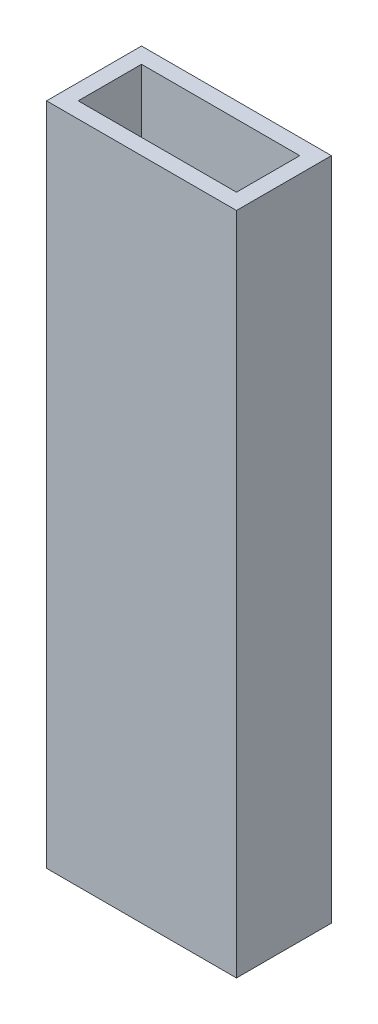
SolidWorks part; units mm, degrees
ref_plane "Front Plane" through (0, 0, 0) normal (0, 0, 1) x (1, 0, 0)
ref_plane "Top Plane" through (0, 0, 0) normal (0, 1, 0) x (1, 0, 0)
ref_plane "Right Plane" through (0, 0, 0) normal (1, 0, 0) x (0, 0, -1)
sketch "Sketch1" plane through (0, 0, 0) normal (0, 1, 0) x (1, 0, 0)
  line L0 (3.175, 15.875) -> (34.925, 15.875)
  line L1 (0, 0) -> (38.1, 0)
  line L2 (0, 0) -> (0, 19.05)
  line L3 (0, 19.05) -> (38.1, 19.05)
  line L4 (38.1, 0) -> (38.1, 19.05)
  line L5 (34.925, 3.175) -> (34.925, 15.875)
  line L6 (3.175, 3.175) -> (34.925, 3.175)
  line L7 (3.175, 3.175) -> (3.175, 15.875)
  dimension "D1" = 38.1
  dimension "D2" = 19.05
extrude "Boss-Extrude1" add sketch "Sketch1" along normal blind 133.35
